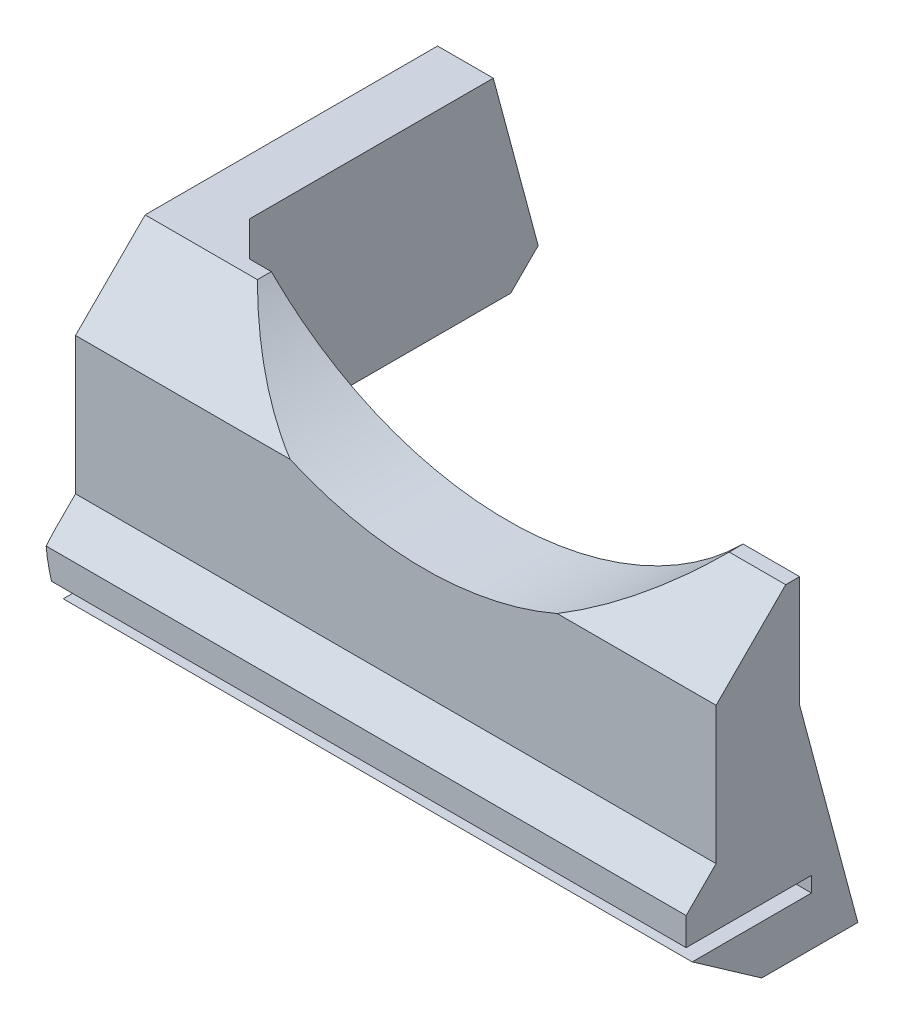
SolidWorks part; units mm, degrees
material "ABS"
ref_plane "Front Plane" through (0, 0, 0) normal (0, 0, 1) x (1, 0, 0)
ref_plane "Top Plane" through (0, 0, 0) normal (0, 1, 0) x (1, 0, 0)
ref_plane "Right Plane" through (0, 0, 0) normal (1, 0, 0) x (0, 0, -1)
sketch "Sketch1" plane through (0, 0, 0) normal (1, 0, 0) x (0, 0, -1)
  line L0 (0, -6) -> (4, -6)
  line L1 (0, -6) -> (-8.5689, 0)
  line L2 (-8.5689, 0) -> (0, 0)
  line L3 (0, 0) -> (0, 1.1)
  line L4 (0, 1.1) -> (-9, 1.1)
  line L5 (-9, 1.1) -> (-9, 3.1)
  line L6 (-6.8499, 12.1) -> (-0.8499, 12.1)
  line L7 (4, -6) -> (-0.8499, 12.1)
  line L8 (-9, 3.1) -> (-6.8499, 5.2501)
  line L9 (-6.8499, 5.2501) -> (-6.8499, 12.1)
  line L10 (-9, 3.1) -> (-9, 12.1) construction
  line L11 (-9, 12.1) -> (-6.8499, 12.1) construction
  dimension "D1" = 6
  dimension "D2" = 35
  dimension "D3" = 4
  dimension "D4" = 105
  dimension "D5" = 1.1
  dimension "D6" = 11
  dimension "D7" = 9
  dimension "D8" = 6
  dimension "D9" = 45
  dimension "D10" = 2
extrude "Boss-Extrude1" add sketch "Sketch1" along normal mid plane 42
sketch "Sketch3" [suppressed] plane through (0, 11.2, 0) normal (0, 1, 0) x (1, 0, 0)
  arc A0 (25, -14.2381) -> (32.5, -21.7381) centre (32.5, -14.2381) ccw construction
  circle A2 centre (32.5, -14.2381) radius 1.75
  point P0 (32.5, -14.2381)
  dimension "D1" = 3.5
extrude "Cut-Extrude1" [suppressed] cut sketch "Sketch3" against normal through all
sketch "Sketch4" [suppressed] plane through (0, 11.2, 0) normal (0, 1, 0) x (1, 0, 0)
  line L1 (35.375, -12.5782) -> (32.5, -10.9184)
  line L2 (32.5, -10.9184) -> (29.625, -12.5782)
  line L3 (29.625, -12.5782) -> (29.625, -15.898)
  line L4 (29.625, -15.898) -> (32.5, -17.5579)
  line L5 (32.5, -17.5579) -> (35.375, -15.898)
  line L6 (35.375, -15.898) -> (35.375, -12.5782)
  arc A0 (25, -14.2381) -> (32.5, -21.7381) centre (32.5, -14.2381) ccw construction
  circle A1 centre (32.5, -14.2381) radius 2.875 construction
  point P0 (32.5, -14.2381)
  dimension "D1" = 5.75
extrude "Cut-Extrude2" [suppressed] cut sketch "Sketch4" against normal blind 3
chamfer "Chamfer2" [suppressed] distance 1 angle 45 tangent propagation no
sketch "Sketch5" plane through (21, 0, 0) normal (1, 0, 0) x (0, 0, -1)
  line L0 (-10, 11.2) -> (-10, 18.7)
  line L1 (-0.8499, 12.1) -> (-6.8499, 12.1) construction
  line L2 (-10, 18.7) -> (-1.4273, 18.7)
  line L3 (-1.4273, 18.7) -> (-0.8499, 12.1)
  line L4 (-0.8499, 12.1) -> (-6.8499, 12.1) construction
  line L12 (-9, 3.1) -> (-9, 1.1)
  line L14 (0, -6) -> (4, -6)
  line L16 (4, -6) -> (-0.8499, 12.1)
  line L17 (-0.8499, 12.1) -> (-6.8499, 12.1)
  line L19 (-9, 1.1) -> (0, 1.1)
  line L20 (0, 1.1) -> (0, 0)
  line L21 (0, 0) -> (-8.5689, 0)
  line L22 (-6.8499, 12.1) -> (-6.8499, 5.2501)
  line L23 (-8.5689, 0) -> (0, -6)
  line L24 (-6.8499, 12.1) -> (-6.8499, 5.2501)
  line L25 (-6.8499, 5.2501) -> (-9, 3.1)
  line L26 (-6.8499, 5.2501) -> (-9, 3.1)
  line L27 (-0.8499, 12.1) -> (-7.6654, 12.1)
  dimension "D1" = 85
  dimension "D2" = 7.5
  dimension "D4" = 0
extrude "Boss-Extrude3" [suppressed] add sketch "Sketch5" against normal up to surface (40 mm away)
sketch "Sketch6" [suppressed] plane through (0, 0, 9) normal (0, 0, 1) x (1, 0, 0)
  line L1 (0, 18.7) -> (40, 18.7) construction
  line L2 (40, 1.2) -> (0.0849, 1.2) construction
  circle A0 centre (20, 36.2) radius 24
  point P4 (20, 18.7)
  point P5 (20, 12.2)
  dimension "D1" = 48
  dimension "D2" = 11
extrude "Cut-Extrude3" [suppressed] cut sketch "Sketch6" against normal through all
chamfer "Chamfer3" [suppressed] distance 1 angle 45
sketch "Sketch7" plane through (0, 0, 6.8499) normal (0, 0, 1) x (1, 0, 0)
  line L0 (0, 12.1) -> (0, 13.1) construction
  line L1 (21, 12.1) -> (-21, 12.1) construction
  line L2 (-21, 12.1) -> (-21, 20.1)
  line L3 (21, 12.1) -> (-21, 12.1)
  line L4 (-21, 20.1) -> (-16.9411, 20.1)
  line L5 (21, 20.1) -> (16.9411, 20.1)
  line L6 (21, 12.1) -> (21, 20.1)
  line L7 (21, 1.1) -> (-21, 1.1) construction
  line L8 (21, 12.1) -> (-21, 12.1) construction
  arc A0 (16.9411, 20.1) -> (-16.9411, 20.1) centre (0, 37.1) cw
  dimension "D1" = 8
  dimension "D2" = 24
  dimension "D3" = 12
extrude "Boss-Extrude4" add sketch "Sketch7" against normal up to vertex (6 mm away) up to point (21, 12.1, 0.8499)
ref_plane "Plane1" through (0, 13.1, 0) normal (0, 1, 0) x (1, 0, 0)
ref_plane "Plane2" through (0, 10.6, 0) normal (0, 1, 0) x (1, 0, 0)
ref_plane "Plane5" through (-2.5, 0, 0) normal (1, 0, 0) x (0, 0, -1)
ref_axis "Axis2" through (-2.5, 10.6, -5.7856) along (0, 0, 1)
ref_plane "Plane3" through (0, 0, 3.8499) normal (0, 0, -1) x (-1, 0, 0)
ref_plane "Plane4" through (0, 0, -0.1501) normal (0, 0, -1) x (-1, 0, 0)
chamfer "Chamfer4" distance 5 angle 45 2 edges at (-18.9705, 20.1, 6.8499) (18.9705, 20.1, 6.8499)
sketch "Sketch15" plane through (-21, 0, 0) normal (-1, 0, 0) x (0, 0, 1)
  line L10 (9, 1.1) -> (9, 3.1)
  line L11 (6.8499, 15.1) -> (1.8499, 20.1)
  line L13 (0.8499, 20.1) -> (0.8499, 12.1)
  line L14 (0.8499, 12.1) -> (-4, -6)
  line L15 (-4, -6) -> (0, -6)
  line L16 (0, -6) -> (8.5689, 0)
  line L17 (8.5689, 0) -> (0, 0)
  line L18 (0, 0) -> (0, 1.1)
  line L19 (0, 1.1) -> (9, 1.1)
  line L20 (9, 1.1) -> (9, 3.1)
  line L21 (6.8499, 15.1) -> (1.8499, 20.1)
  line L23 (0.8499, 20.1) -> (0.8499, 12.1)
  line L24 (0.8499, 12.1) -> (-4, -6)
  line L25 (-4, -6) -> (0, -6)
  line L26 (0, -6) -> (8.5689, 0)
  line L27 (8.5689, 0) -> (0, 0)
  line L28 (0, 0) -> (0, 1.1)
  line L29 (0, 1.1) -> (9, 1.1)
  line L30 (1.8499, 20.1) -> (0.8499, 20.1)
  line L31 (1.8499, 20.1) -> (0.8499, 20.1)
  line L34 (6.8499, 5.2501) -> (6.8499, 15.1)
  line L35 (6.8499, 5.2501) -> (6.8499, 15.1)
  line L36 (9, 3.1) -> (6.8499, 5.2501)
  line L37 (9, 3.1) -> (6.8499, 5.2501)
  dimension "D1" = 0
extrude "Boss-Extrude5" add sketch "Sketch15" along normal blind 4
sketch "Sketch16" plane through (0, 0, 0) normal (0, 0, 1) x (1, 0, 0)
  line L0 (-25, 1.1) -> (-20, 3.9868)
  line L1 (-20, 3.9868) -> (-20, 20.1)
  line L2 (-25, 20.1) -> (-16.9411, 20.1) construction
  line L3 (21, 1.1) -> (-25, 1.1) construction
  line L4 (-20, 20.1) -> (-25, 20.1)
  line L5 (-25, 20.1) -> (-25, 1.1)
  dimension "D1" = 30
  dimension "D2" = 5
extrude "Cut-Extrude4" [suppressed] cut sketch "Sketch16" against normal through all and the other way through all
sketch "Sketch22" plane through (-25, 0, 0) normal (-1, 0, 0) x (0, 0, 1)
  line L0 (0.8499, 6.1) -> (0.8499, 1.1)
  line L1 (0.8499, 20.1) -> (-19.1501, 20.1)
  line L2 (0.8499, 20.1) -> (0.8499, 6.1)
  line L3 (-4.1501, 6.1) -> (-19.1501, 6.1)
  line L4 (-19.1501, 20.1) -> (-19.1501, 6.1) construction
  line L5 (0, 1.1) -> (9, 1.1) construction
  line L6 (0.8499, 1.1) -> (-4.1501, 6.1)
  line L7 (-4.1501, 6.1) -> (0.8499, 6.1) construction
  line L8 (-19.1501, 20.1) -> (-22.9014, 6.1)
  line L9 (-22.9014, 6.1) -> (-19.1501, 6.1)
  line L10 (0.8499, 12.1) -> (-4, -6) construction
  dimension "D1" = 45
  dimension "D2" = 5
  dimension "D3" = 20
extrude "Boss-Extrude10" add sketch "Sketch22" against normal blind 4
fillet "Fillet1" radius 10 1 edges at (-25, -6, -2)
chamfer "Chamfer5" distance 2.5 angle 45 3 edges at (21, -6, -2) (-21, 16.1, 0.8499) (-23, 6.1, -22.9014) first distance on face at (3, -6, -2) first distance on face at (-21, 11.3208, -7.6628) first distance on face at (-23, 6.1, -13.5258)
sketch "Sketch17" plane through (0, 0, 0) normal (0, 0, 1) x (1, 0, 0)
  line L1 (-4.5, 11.725) -> (4.5, 11.725)
  line L2 (-4.5, 11.725) -> (-4.5, 10.475)
  line L3 (-4.5, 10.475) -> (4.5, 10.475)
  line L4 (4.5, 11.725) -> (4.5, 10.475)
  line L5 (-4.5, 11.725) -> (4.5, 10.475) construction
  line L6 (-4.5, 10.475) -> (4.5, 11.725) construction
  arc A0 (-16.9411, 20.1) -> (16.9411, 20.1) centre (0, 37.1) ccw construction
  point P0 (0, 11.1)
  point P5 (0, 13.1)
  dimension "D1" = 9
  dimension "D2" = 1.25
  dimension "D3" = 2
extrude "Cut-Extrude5" [suppressed] cut sketch "Sketch17" along normal through all
sketch "Sketch18" [suppressed] plane through (0, 0, 6.8499) normal (0, 0, 1) x (1, 0, 0)
  line L0 (-4.5, 10.475) -> (4.5, 10.475) construction
  line L1 (-4, 10.475) -> (4, 10.475)
  line L2 (-4, 10.475) -> (-4, 1.1)
  line L3 (-4, 1.1) -> (4, 1.1)
  line L4 (4, 10.475) -> (4, 1.1)
  line L6 (20, 1.1) -> (-23.5703, 1.1) construction
  point P4 (0, 10.475)
  point P7 (0, 10.475)
  dimension "D1" = 8
extrude "Boss-Extrude6" [suppressed] add sketch "Sketch18" along normal blind 4
sketch "Sketch19" [suppressed] plane through (0, 10.475, 0) normal (0, 1, 0) x (1, 0, 0)
  line L0 (0, -6.8499) -> (0, -10.8499) construction
  line L1 (-9.5917, -6.8499) -> (9.5917, -6.8499) construction
  line L2 (4, -10.8499) -> (-4, -10.8499) construction
  line L3 (4, -6.8499) -> (4, -10.8499)
  line L4 (4, -10.8499) -> (8, -6.8499)
  line L5 (20, -6.8499) -> (4, -6.8499) construction
  line L6 (4, -6.8499) -> (8, -6.8499)
  line L7 (-4, -6.8499) -> (-8, -6.8499)
  line L8 (-4, -10.8499) -> (-8, -6.8499)
  line L9 (-4, -6.8499) -> (-4, -10.8499)
extrude "Boss-Extrude8" [suppressed] add sketch "Sketch19" against normal up to surface (9.375 mm away)
